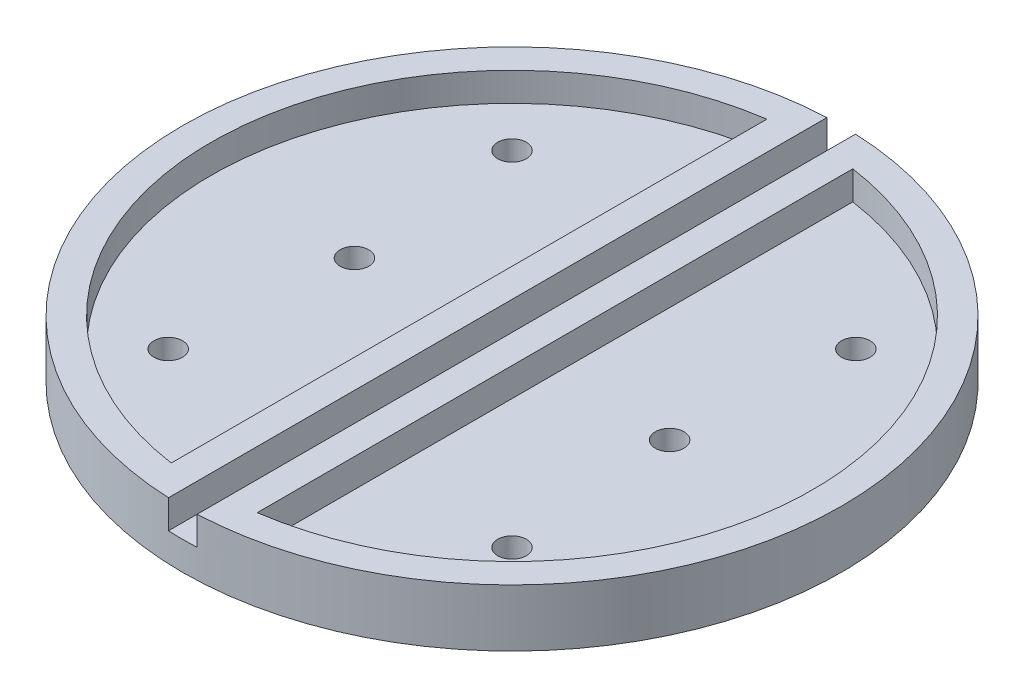
SolidWorks part; units mm, degrees
material "ABS"
ref_plane "Front Plane" through (0, 0, 0) normal (0, 0, 1) x (1, 0, 0)
ref_plane "Top Plane" through (0, 0, 0) normal (0, 1, 0) x (1, 0, 0)
ref_plane "Right Plane" through (0, 0, 0) normal (1, 0, 0) x (0, 0, -1)
sketch "Sketch5" plane through (0, 0, 0) normal (0, 1, 0) x (1, 0, 0)
  circle A0 centre (0, 0) radius 73.025
  circle A1 centre (38.1, 38.1) radius 3.175
  circle A2 centre (38.1, -38.1) radius 3.175
  circle A3 centre (-38.1, 38.1) radius 3.175
  circle A4 centre (-38.1, -38.1) radius 3.175
extrude "PlateBase" add sketch "Sketch5" along normal blind 6.35
sketch "Sketch6" plane through (0, 6.35, 0) normal (0, 1, 0) x (1, 0, 0)
  line L1 (3.175, 0) -> (3.175, 72.9559)
  line L3 (3.175, 0) -> (3.175, -72.9559)
  line L4 (0, 0) -> (3.175, 0)
  line L5 (-3.175, 0) -> (-3.175, 72.9559)
  line L6 (-9.525, 0) -> (-9.525, 72.4011)
  line L7 (-9.525, 0) -> (-9.525, -72.4011)
  line L8 (-3.175, 0) -> (-3.175, -72.9559)
  line L9 (9.525, 0) -> (9.525, 72.4011)
  line L10 (9.525, 0) -> (9.525, -72.4011)
  circle A0 centre (0, 0) radius 73.025 construction
  circle M4 centre (0, 0) radius 73.025
extrude "PlateTop" add sketch "Sketch6" along normal blind 6.35 contours L8 L5 L6 L7 M4 | L10 L9 L1 L3 M4 region at (6.346, 6.35, 0) region at (-6.346, 6.35, 0)
sketch "Sketch9" plane through (0, 6.35, 0) normal (0, 1, 0) x (1, 0, 0)
  circle A0 centre (0, 0) radius 66.675
  circle A1 centre (0, 0) radius 73.025
extrude "PlateWalls" add sketch "Sketch9" along normal blind 6.35
sketch "Sketch11" plane through (0, 12.7, 0) normal (0, 1, 0) x (1, 0, 0)
  line L0 (-3.175, 66.5994) -> (-3.175, 72.9559)
  line L1 (3.175, 66.5994) -> (3.175, 72.9559)
  line L2 (-3.175, 66.5994) -> (3.175, 66.5994)
  circle A0 centre (0, 0) radius 73.025 construction
  arc A1 (-3.175, 72.9559) -> (3.175, 72.9559) centre (0, 0) cw
extrude "TopSlotCut" cut sketch "Sketch11" against normal blind 6.35
sketch "Sketch12" plane through (0, 12.7, 0) normal (0, 1, 0) x (1, 0, 0)
  line L0 (-3.175, -66.5994) -> (-3.175, -72.9559)
  line L1 (3.175, -66.5994) -> (3.175, -72.9559)
  line L2 (-3.175, -66.5994) -> (3.175, -66.5994)
  arc A0 (-3.175, 72.9559) -> (3.175, 72.9559) centre (0, 0) ccw construction
  arc A1 (3.175, -72.9559) -> (-3.175, -72.9559) centre (0, 0) cw
extrude "BottomSlotCut" cut sketch "Sketch12" against normal blind 6.35
sketch "Sketch13" plane through (0, 6.35, 0) normal (0, 1, 0) x (1, 0, 0)
  circle A0 centre (34.925, 0) radius 3.175
extrude "RightThruHole" cut sketch "Sketch13" against normal blind 6.35
sketch "Sketch14" plane through (0, 6.35, 0) normal (0, 1, 0) x (1, 0, 0)
  circle A0 centre (-34.925, 0) radius 3.175
extrude "LeftThruHole" cut sketch "Sketch14" against normal blind 6.35
